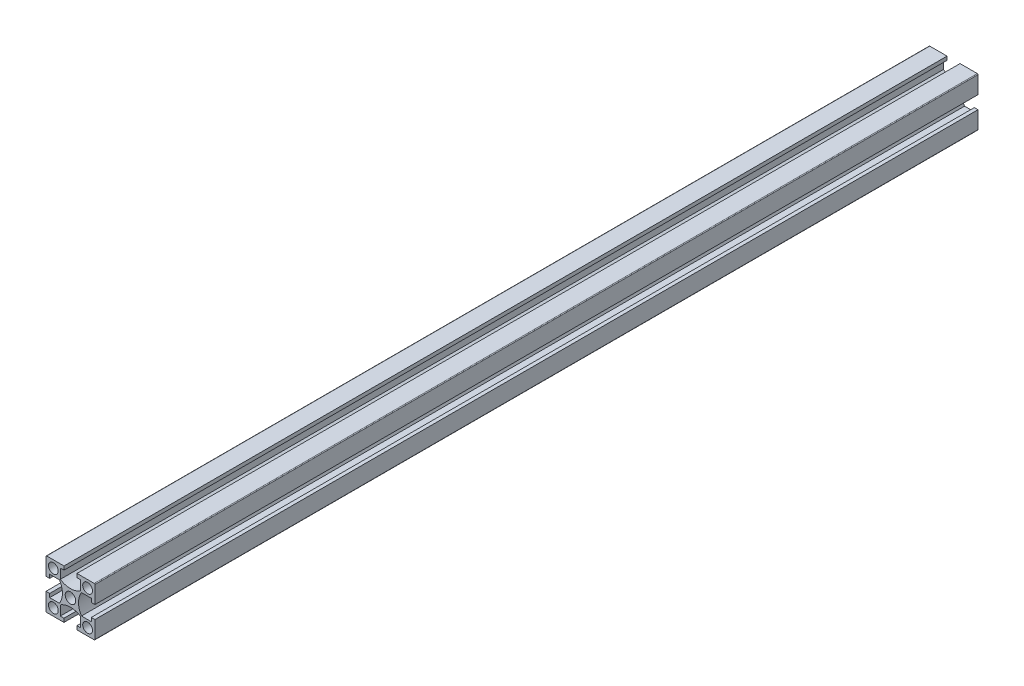
SolidWorks part; units mm, degrees
material "3.0255 (EN-AW 1350A)"
ref_plane "정면" through (0, 0, 0) normal (0, 0, 1) x (1, 0, 0)
ref_plane "윗면" through (0, 0, 0) normal (0, 1, 0) x (1, 0, 0)
ref_plane "우측면" through (0, 0, 0) normal (1, 0, 0) x (0, 0, -1)
sketch "스케치1" plane through (0, 0, 0) normal (0, 0, 1) x (1, 0, 0)
  line L0 (0, 32.0265) -> (0, -31.6588) construction
  line L1 (-10, 10) -> (-10, -10)
  line L2 (-10, 10) -> (10, 10)
  line L3 (-10, 2.65) -> (-8.5, 2.65)
  line L4 (13.6618, 0) -> (-11.6993, 0) construction
  line L5 (-8.5, 2.65) -> (-8.5, 4.15)
  line L6 (-8.5, 4.15) -> (-4.5032, 4.15)
  line L7 (-10, -2.65) -> (-8.5, -2.65)
  line L8 (-8.5, -2.65) -> (-8.5, -4.15)
  line L9 (-8.5, -4.15) -> (-4.5032, -4.15)
  line L10 (-10, -10) -> (10, -10)
  line L11 (10, 10) -> (10, -10)
  circle A0 centre (-7, 7) radius 2
  circle A1 centre (-7, -7) radius 2
  arc A2 (-4.5032, 4.15) -> (-4.5032, -4.15) centre (-11.0587, 0) cw
  circle A3 centre (0, 0) radius 2.15
  circle A4 centre (7, 7) radius 2
  circle A5 centre (7, -7) radius 2
  point P21 (-10, 0)
  point P23 (-3.3, 0)
  point P31 (0, -10)
  point P32 (0, 10)
  dimension "D3" = 4
  dimension "D9" = 6.7
  dimension "D10" = 4.3
  dimension "D11" = 7.7587
  dimension "D1" = 20
  dimension "D2" = 20
  dimension "D4" = 14
  dimension "D5" = 14
  dimension "D6" = 5.3
  dimension "D7" = 8.3
  dimension "D8" = 1.5
extrude "보스-돌출1" add sketch "스케치1" along normal blind 361 contours A0 | A4 | A3 | A5 | A1 | A2 L6 L5 L3 L1 L7 L8 L9 | L2 L11 L10 L1 region at (-6.6069, 0, 0) region at (-7, 7, 0) region at (-7, -7, 0) region at (0, 0, 0) region at (7, 7, 0) region at (7, -7, 0)
extrude "컷-돌출1" cut sketch "스케치1<3>" along normal up to next contours A2 L6 L5 L3 L1 L7 L8 L9 region at (-6.6069, 0, 0)
sketch "스케치1<3>" plane through (0, 0, 0) normal (0, 0, 1) x (1, 0, 0) same geometry as "스케치1"
pattern_circular "원형 패턴1" count 4 over 360 about axis through (0, 0, 361) along (0, 0, -1) of "컷-돌출1" reverse direction yes
fillet "필렛1" radius 0.3 4 edges at (10, -10, 180.5) (-10, -10, 180.5) (-10, 10, 180.5) (10, 10, 180.5)
sketch "스케치3" plane through (0, 10, 0) normal (0, 1, 0) x (1, 0, 0)
  circle A0 centre (0, -11) radius 2.5
  circle A1 centre (0, -250) radius 2.5
  dimension "D1" = 11
  dimension "D3" = 239
extrude "컷-돌출2" cut sketch "스케치3" against normal through all
sketch "스케치4" plane through (0, 10, 0) normal (0, 1, 0) x (1, 0, 0)
  line L0 (-4.15, -361) -> (4.15, -361) construction
  circle A1 centre (0, -56) radius 2.15
  circle A2 centre (0, -108) radius 2.15
  circle A3 centre (0, -11) radius 2.5 construction
  circle A4 centre (0, -351) radius 2.15
  circle A5 centre (0, -271) radius 2.15
  dimension "D1" = 10
  dimension "D2" = 52
  dimension "D3" = 97
  dimension "D4" = 80
extrude "컷-돌출3" cut sketch "스케치4" against normal through all
